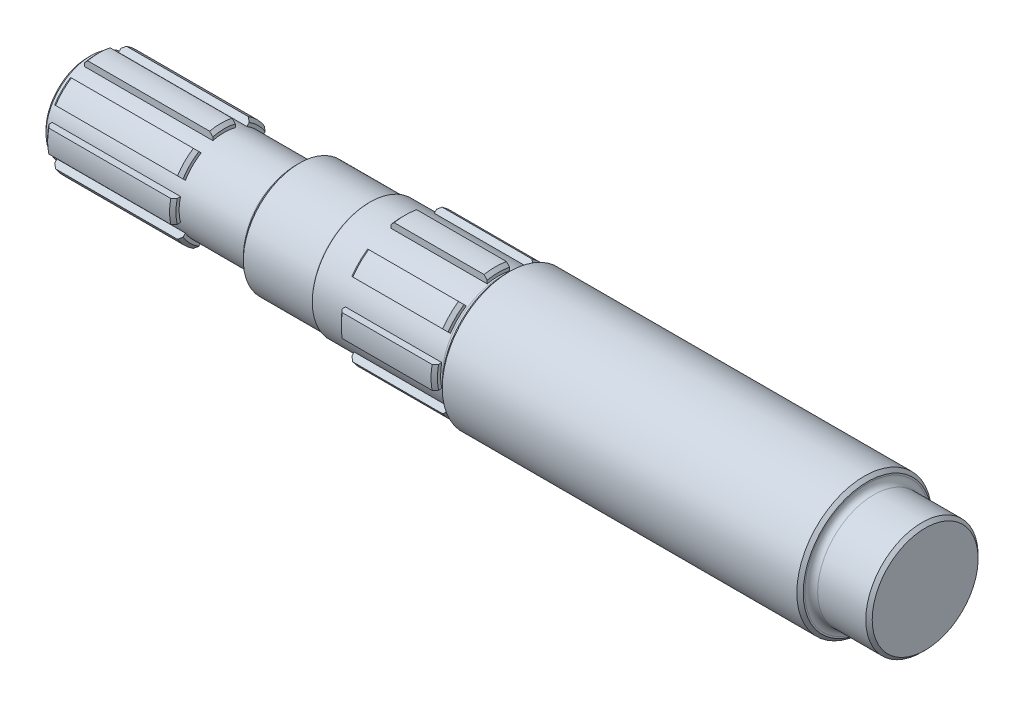
SolidWorks part; units mm, degrees
ref_plane "Front Plane" through (0, 0, 0) normal (0, 0, 1) x (1, 0, 0)
ref_plane "Top Plane" through (0, 0, 0) normal (0, 1, 0) x (1, 0, 0)
ref_plane "Right Plane" through (0, 0, 0) normal (1, 0, 0) x (0, 0, -1)
sketch "Sketch1" plane through (0, 0, 0) normal (0, 0, 1) x (1, 0, 0)
  line L0 (-88.5202, 0) -> (101.5471, 0) construction
  line L1 (-80.5157, 0) -> (-80.5157, 17.5)
  line L2 (-80.5157, 17.5) -> (-57.5157, 17.5)
  line L3 (-57.5157, 17.5) -> (-57.5157, 18)
  line L4 (-57.5157, 18) -> (-47.5157, 18)
  line L5 (-15.0157, 18) -> (-15.0157, 21)
  line L6 (-15.0157, 21) -> (97.4843, 21)
  line L7 (97.4843, 21) -> (97.4843, 17.5)
  line L8 (97.4843, 17.5) -> (115.4843, 17.5)
  line L9 (115.4843, 17.5) -> (115.4843, 0)
  line L10 (-80.5157, 0) -> (115.4843, 0)
  line L11 (-47.5157, 18) -> (-47.5157, 20)
  line L12 (-47.5157, 20) -> (-17.5157, 20)
  line L13 (-17.5157, 20) -> (-17.5157, 18)
  line L14 (-17.5157, 18) -> (-15.0157, 18)
  point P5 (-32.5157, 18)
  dimension "D1" = 17.5
  dimension "D2" = 23
  dimension "D3" = 42.5
  dimension "D4" = 112.5
  dimension "D5" = 18
  dimension "D6" = 21
  dimension "D7" = 17.5
  dimension "D8" = 18
  dimension "D9" = 25
  dimension "D10" = 15
  dimension "D11" = 15
  dimension "D12" = 20
revolve "Revolve1" add sketch "Sketch1" angle 360 about L0
sketch "Sketch2" plane through (-80.5157, 0, 0) normal (-1, 0, 0) x (0, 0, 1)
  circle A2 centre (0, 0) radius 14
  dimension "D1" = 28
extrude "Boss-Extrude1" add sketch "Sketch2" along normal blind 65
sketch "Sketch3" plane through (-47.5157, 0, 0) normal (-1, 0, 0) x (0, 0, 1)
  line L0 (0, 0) -> (0, 24.1209) construction
  line L1 (3.5, 19.6914) -> (3.5, 17.6564)
  line L2 (-3.5, 19.6914) -> (-3.5, 17.6564)
  line L3 (11.449, 16.3988) -> (10.0101, 14.9599)
  line L4 (16.3988, 11.449) -> (14.9599, 10.0101)
  line L5 (19.6914, 3.5) -> (17.6564, 3.5)
  line L6 (19.6914, -3.5) -> (17.6564, -3.5)
  line L7 (16.3988, -11.449) -> (14.9599, -10.0101)
  line L8 (11.449, -16.3988) -> (10.0101, -14.9599)
  line L9 (3.5, -19.6914) -> (3.5, -17.6564)
  line L10 (-3.5, -19.6914) -> (-3.5, -17.6564)
  line L11 (-11.449, -16.3988) -> (-10.0101, -14.9599)
  line L12 (-16.3988, -11.449) -> (-14.9599, -10.0101)
  line L13 (-19.6914, -3.5) -> (-17.6564, -3.5)
  line L14 (-19.6914, 3.5) -> (-17.6564, 3.5)
  line L15 (-16.3988, 11.449) -> (-14.9599, 10.0101)
  line L16 (-11.449, 16.3988) -> (-10.0101, 14.9599)
  circle A3 centre (0, 0) radius 18 construction
  circle A23 centre (0, 0) radius 18 construction
  circle A24 centre (0, 0) radius 20 construction
  arc A25 (-14.9599, 10.0101) -> (-17.6564, 3.5) centre (0, 0) ccw
  arc A26 (-16.3988, 11.449) -> (-19.6914, 3.5) centre (0, 0) ccw
  arc A27 (-19.6914, -3.5) -> (-16.3988, -11.449) centre (0, 0) ccw
  arc A28 (-17.6564, -3.5) -> (-14.9599, -10.0101) centre (0, 0) ccw
  arc A29 (-11.449, -16.3988) -> (-3.5, -19.6914) centre (0, 0) ccw
  arc A30 (-10.0101, -14.9599) -> (-3.5, -17.6564) centre (0, 0) ccw
  arc A31 (3.5, -19.6914) -> (11.449, -16.3988) centre (0, 0) ccw
  arc A32 (3.5, -17.6564) -> (10.0101, -14.9599) centre (0, 0) ccw
  arc A33 (16.3988, -11.449) -> (19.6914, -3.5) centre (0, 0) ccw
  arc A34 (14.9599, -10.0101) -> (17.6564, -3.5) centre (0, 0) ccw
  arc A35 (19.6914, 3.5) -> (16.3988, 11.449) centre (0, 0) ccw
  arc A36 (17.6564, 3.5) -> (14.9599, 10.0101) centre (0, 0) ccw
  arc A37 (11.449, 16.3988) -> (3.5, 19.6914) centre (0, 0) ccw
  arc A38 (10.0101, 14.9599) -> (3.5, 17.6564) centre (0, 0) ccw
  arc A39 (-3.5, 19.6914) -> (-11.449, 16.3988) centre (0, 0) ccw
  arc A40 (-3.5, 17.6564) -> (-10.0101, 14.9599) centre (0, 0) ccw
  point P40 (0, 0)
  dimension "D1" = 8
  dimension "D2" = 2.0349
extrude "Cut-Extrude1" cut sketch "Sketch3" against normal blind 30
fillet "Fillet1" radius 2 1 edges at (-15.0157, 0, 18)
fillet "Fillet2" radius 2 1 edges at (97.4843, 0, 17.5)
fillet "Fillet3" radius 0.5 1 edges at (-57.5157, 0, 17.5)
ref_plane "Plane1" through (-143.0157, 0, 0) normal (-1, 0, 0) x (0, 0, 1)
chamfer "Chamfer1" distance 1 angle 45 16 edges at (-47.5157, -20, 0) (-47.5157, -14.1421, 14.1421) (-47.5157, 0, 20) (-47.5157, -12.7279, -12.7279) (-47.5157, 0, -20) (-47.5157, 14.1421, 14.1421) (-47.5157, 20, 0) (-47.5157, 14.1421, -14.1421) (-17.5157, 20, 0) (-17.5157, 14.1421, 14.1421) (-17.5157, 0, 20) (-17.5157, -14.1421, 14.1421) (-17.5157, -20, 0) (-17.5157, -14.1421, -14.1421) (-17.5157, 0, -20) (-17.5157, 14.1421, -14.1421)
sketch "Sketch6" plane through (-143.0157, 0, 0) normal (-1, 0, 0) x (0, 0, 1)
  line L0 (0, 0) -> (0, 21.7594) construction
  line L1 (-3.5, 15.6125) -> (-3.5, 13.5554)
  line L3 (3.5, 15.6125) -> (3.5, 13.5554)
  line L4 (13.5146, 8.5648) -> (12.06, 7.1103)
  line L5 (8.5648, 13.5146) -> (7.1103, 12.06)
  line L6 (15.6125, -3.5) -> (13.5554, -3.5)
  line L7 (15.6125, 3.5) -> (13.5554, 3.5)
  line L8 (8.5648, -13.5146) -> (7.1103, -12.06)
  line L9 (13.5146, -8.5648) -> (12.06, -7.1103)
  line L10 (-3.5, -15.6125) -> (-3.5, -13.5554)
  line L11 (3.5, -15.6125) -> (3.5, -13.5554)
  line L12 (-13.5146, -8.5648) -> (-12.06, -7.1103)
  line L13 (-8.5648, -13.5146) -> (-7.1103, -12.06)
  line L14 (-15.6125, 3.5) -> (-13.5554, 3.5)
  line L15 (-15.6125, -3.5) -> (-13.5554, -3.5)
  line L16 (-8.5648, 13.5146) -> (-7.1103, 12.06)
  line L17 (-13.5146, 8.5648) -> (-12.06, 7.1103)
  arc A0 (-15.6125, 3.5) -> (-15.6125, -3.5) centre (0, 0) ccw
  circle A13 centre (0, 0) radius 16 construction
  circle A14 centre (0, 0) radius 14 construction
  arc A15 (-13.5554, 3.5) -> (-13.5554, -3.5) centre (0, 0) ccw
  circle A16 centre (0, 0) radius 14 construction
  arc A17 (-7.1103, 12.06) -> (-12.06, 7.1103) centre (0, 0) ccw
  arc A18 (-8.5648, 13.5146) -> (-13.5146, 8.5648) centre (0, 0) ccw
  arc A19 (-12.06, -7.1103) -> (-7.1103, -12.06) centre (0, 0) ccw
  arc A20 (-13.5146, -8.5648) -> (-8.5648, -13.5146) centre (0, 0) ccw
  arc A21 (-3.5, -13.5554) -> (3.5, -13.5554) centre (0, 0) ccw
  arc A22 (-3.5, -15.6125) -> (3.5, -15.6125) centre (0, 0) ccw
  arc A23 (7.1103, -12.06) -> (12.06, -7.1103) centre (0, 0) ccw
  arc A24 (8.5648, -13.5146) -> (13.5146, -8.5648) centre (0, 0) ccw
  arc A25 (13.5554, -3.5) -> (13.5554, 3.5) centre (0, 0) ccw
  arc A26 (15.6125, -3.5) -> (15.6125, 3.5) centre (0, 0) ccw
  arc A27 (12.06, 7.1103) -> (7.1103, 12.06) centre (0, 0) ccw
  arc A28 (13.5146, 8.5648) -> (8.5648, 13.5146) centre (0, 0) ccw
  arc A29 (3.5, 13.5554) -> (-3.5, 13.5554) centre (0, 0) ccw
  arc A30 (3.5, 15.6125) -> (-3.5, 15.6125) centre (0, 0) ccw
  point P8 (13.3883, 4.0932)
  point P12 (16, 0)
  point P31 (0, 0)
  point P42 (0, 0)
  dimension "D1" = 3.5
  dimension "D2" = 0
  dimension "D4" = 2
extrude "Boss-Extrude4" add sketch "Sketch6" against normal blind 40
chamfer "Chamfer3" distance 1 angle 45 17 edges at (-145.5157, 0, 14) (-143.0157, 16, 0) (-103.0157, 16, 0) (-103.0157, 11.3137, 11.3137) (-143.0157, 0, 16) (-143.0157, 11.3137, 11.3137) (-103.0157, 0, 16) (-143.0157, -11.3137, 11.3137) (-103.0157, -11.3137, 11.3137) (-143.0157, -16, 0) (-103.0157, -16, 0) (-143.0157, -11.3137, -11.3137) (-103.0157, -11.3137, -11.3137) (-143.0157, 0, -16) (-103.0157, 0, -16) (-103.0157, 11.3137, -11.3137) (-143.0157, 11.3137, -11.3137)
chamfer "Chamfer4" distance 1 angle 45 1 edges at (-80.5157, 0, 17.5)
fillet "Fillet4" radius 2 1 edges at (-80.5157, 0, 14)
chamfer "Chamfer5" distance 1 angle 45 1 edges at (-15.0157, 0, 21)
chamfer "Chamfer7" distance 1 angle 45 1 edges at (97.4843, 0, 21)
chamfer "Chamfer8" distance 1 angle 45 1 edges at (115.4843, 0, 17.5)
